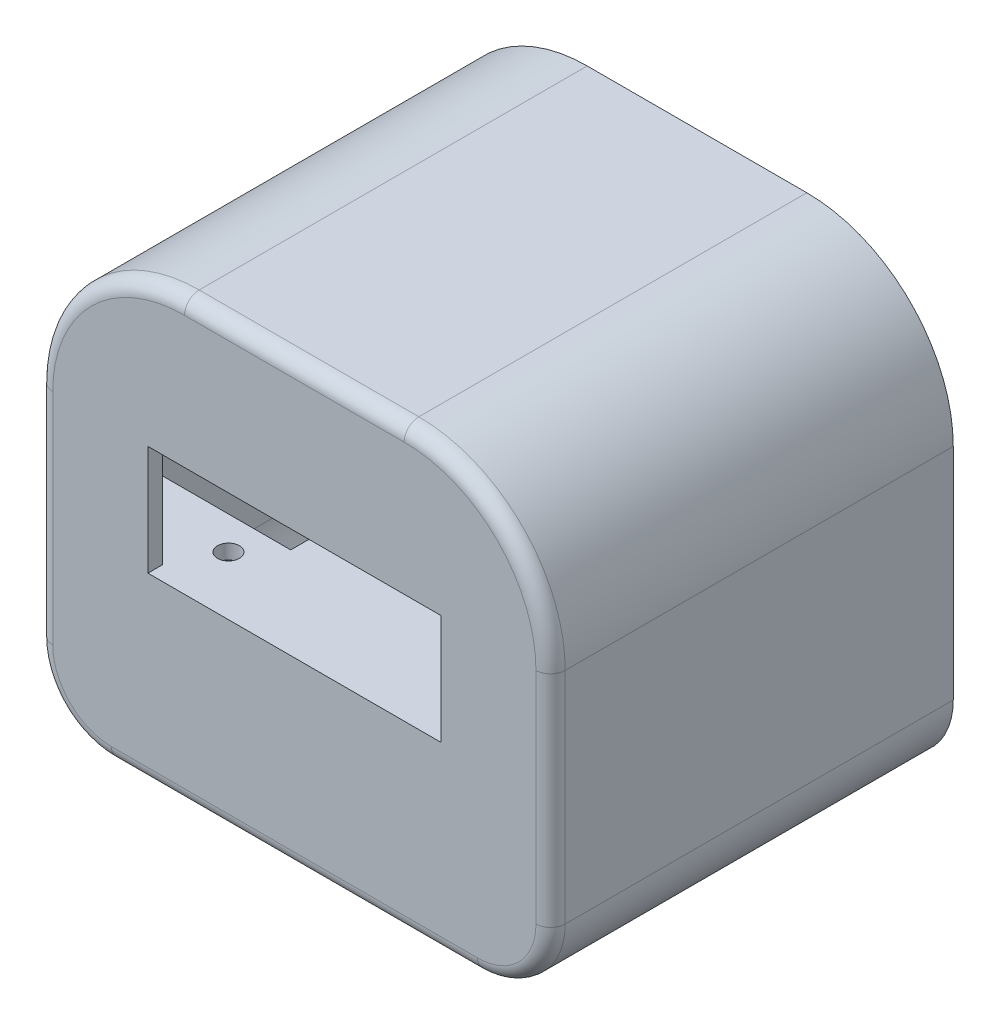
SolidWorks part; units mm, degrees
ref_plane "Front Plane" through (0, 0, 0) normal (0, 0, 1) x (1, 0, 0)
ref_plane "Top Plane" through (0, 0, 0) normal (0, 1, 0) x (1, 0, 0)
ref_plane "Right Plane" through (0, 0, 0) normal (1, 0, 0) x (0, 0, -1)
sketch "Sketch1" plane through (0, 0, 0) normal (0, 0, 1) x (1, 0, 0)
  line L1 (-15, 30) -> (15, 30)
  line L2 (-35, 10) -> (-35, -20)
  line L3 (-25, -30) -> (25, -30)
  line L4 (35, 10) -> (35, -20)
  line L5 (-35, 30) -> (35, -30) construction
  line L6 (-35, -30) -> (35, 30) construction
  arc A0 (25, -30) -> (35, -20) centre (25, -20) ccw
  arc A1 (-35, -20) -> (-25, -30) centre (-25, -20) ccw
  arc A2 (15, 30) -> (35, 10) centre (15, 10) cw
  arc A3 (-15, 30) -> (-35, 10) centre (-15, 10) ccw
  point P0 (0, 0)
  dimension "D1" = 20
  dimension "D4" = 10
  dimension "D2" = 70
  dimension "D3" = 60
extrude "Boss-Extrude1" add sketch "Sketch1" along normal blind 55
shell "Shell1" thickness 2 removed face at (0, -1.9822, 0)
sketch "Sketch2" plane through (0, 0, 0) normal (0, 0, -1) x (-1, 0, 0)
  line L0 (-15, 30) -> (15, 30) construction
  line L1 (-15, 18.48) -> (-30.8773, 18.48)
  line L2 (-15, 18.48) -> (-15, 28)
  line L3 (0, 28) -> (0, -28) construction
  line L4 (-15, 28) -> (15, 28) construction
  line L5 (25, -28) -> (-25, -28) construction
  line L6 (15, 18.48) -> (15, 28)
  line L7 (15, 18.48) -> (30.8773, 18.48)
  arc A0 (-15, 28) -> (-33, 10) centre (-15, 10) ccw construction
  arc A1 (-30.8773, 18.48) -> (-15, 28) centre (-15, 10) cw
  arc A2 (30.8773, 18.48) -> (15, 28) centre (15, 10) ccw
  dimension "D1" = 11.52
extrude "Boss-Extrude2" add sketch "Sketch2" against normal blind 10 contours L7 A2 L6 | L1 A1 L2
hole_wizard "M3x0.5 Tapped Hole1" positions "Sketch3" profile "Sketch4" tap size "M3x0.5" standard "ANSI Metric"
sketch "Sketch3" plane through (0, 0, 0) normal (0, 0, -1) x (-1, 0, 0)
  line L0 (-15, 30) -> (15, 30) construction
  line L1 (-35, -20) -> (-35, 10) construction
  line L2 (35, 10) -> (35, -20) construction
  point P0 (-18.11, 22)
  point P10 (21.89, 22)
  dimension "D1" = 8
  dimension "D2" = 16.89
  dimension "D3" = 13.11
sketch "Sketch4" plane through (18.11, 22, 0) normal (1, 0, 0) x (0, 1, 0)
  line L0 (0, 0) -> (0, 8.2511)
  line L1 (0, 8.2511) -> (1.25, 7.5)
  line L2 (1.25, 7.5) -> (1.25, 0)
  line L5 (1.25, 0) -> (0, 0)
  line L10 (0, 8.2511) -> (-1.25, 7.5) construction
  line L11 (0, -6.35) -> (0, 107.95) construction
  dimension "Tap Drill Dia." = 2.5
  dimension "Tap Drill Depth" = 7.5
  dimension "Drill Angle" = 118
sketch "Sketch5" plane through (0, 0, 0) normal (0, 0, -1) x (-1, 0, 0)
  line L1 (-33, -5) -> (33, -5)
  line L2 (-33, -5) -> (-33, -7)
  line L3 (-33, -7) -> (33, -7)
  line L4 (33, -5) -> (33, -7)
  line L5 (33, 10) -> (33, -20) construction
  line L7 (-15, 30) -> (15, 30) construction
  dimension "D1" = 35
  dimension "D2" = 2
extrude "Boss-Extrude3" add sketch "Sketch5" against normal up to next contours L1 L4 L3 L2
sketch "Sketch6" plane through (0, 0, 53) normal (0, 0, -1) x (-1, 0, 0)
  line L0 (-33, -5) -> (33, -5) construction
  line L1 (-20, -5) -> (20, -5)
  line L2 (-20, -5) -> (-20, 10)
  line L3 (-20, 10) -> (20, 10)
  line L4 (20, -5) -> (20, 10)
  point P6 (0, 10)
  dimension "D1" = 15
  dimension "D2" = 40
extrude "Cut-Extrude1" cut sketch "Sketch6" against normal blind 10
hole_wizard "Ø3.0mm Dowel Hole1" positions "Sketch7" profile "Sketch8" hole size "Ø3.0" standard "AS"
sketch "Sketch7" plane through (0, -5, 0) normal (0, 1, 0) x (1, 0, 0)
  line L0 (17, -34.5) -> (-17, -47) construction
  line L2 (-20, -55) -> (20, -55) construction
  line L3 (-17, -47) -> (-17, -22) construction
  point P0 (-17, -47)
  point P2 (-17, -22)
  point P4 (17, -34.5)
  point P11 (0, -40.75)
  point P14 (0, -55)
  point P20 (-17, -34.5)
  dimension "D1" = 25
  dimension "D2" = 34
  dimension "D3" = 8
sketch "Sketch8" plane through (-17, -5, 47) normal (1, 0, 0) x (0, 0, 1)
  line L0 (0, 0) -> (0, 4.9013)
  line L1 (0, 4.9013) -> (1.5, 4)
  line L2 (1.5, 4) -> (1.5, 0)
  line L5 (1.5, 0) -> (0, 0)
  line L10 (0, 4.9013) -> (-1.5, 4) construction
  line L11 (0, -6.35) -> (0, 107.95) construction
  dimension "Hole Dia." = 3
  dimension "Hole Depth" = 4
  dimension "Drill Angle" = 118
sketch "Sketch9" plane through (0, -5, 0) normal (0, 1, 0) x (1, 0, 0)
  line L0 (-33, -53) -> (-33, 0) construction
  line L1 (-33, -26.5) -> (-13, -26.5)
  line L2 (-33, -26.5) -> (-33, -42.5)
  line L3 (-33, -42.5) -> (-13, -42.5)
  line L4 (-13, -26.5) -> (-13, -42.5)
  line L5 (-17, -47) -> (-17, -22) construction
  point P6 (-17, -34.5)
  point P7 (-13, -34.5)
  dimension "D1" = 20
extrude "Cut-Extrude2" cut sketch "Sketch9" against normal up to surface (2 mm away) up to face at (-15.5, -7, 47)
fillet "Fillet1" radius 2 8 edges at (35, -5, 55) (32.0711, -27.0711, 55) (0, -30, 55) (-32.0711, -27.0711, 55) (-35, -5, 55) (-29.1421, 24.1421, 55) (0, 30, 55) (29.1421, 24.1421, 55)
